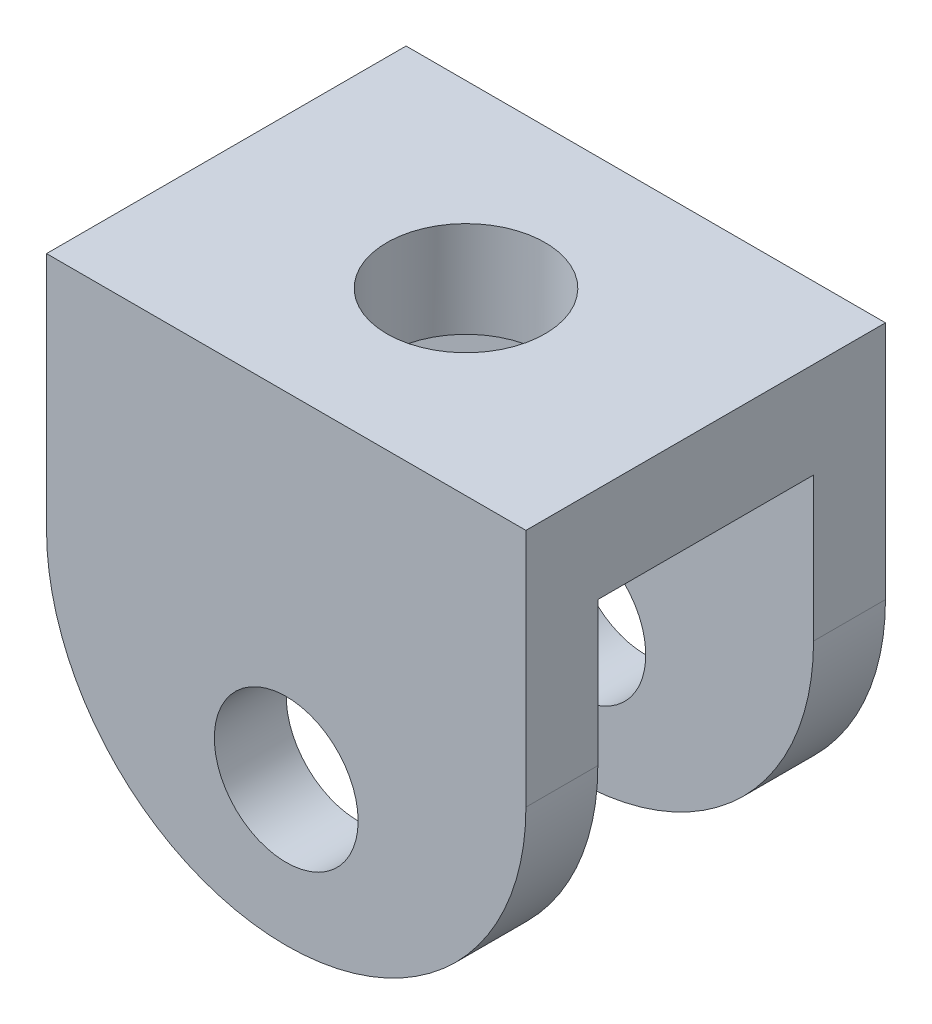
SolidWorks part; units mm, degrees
ref_plane "Front Plane" through (0, 0, 0) normal (0, 0, 1) x (1, 0, 0)
ref_plane "Top Plane" through (0, 0, 0) normal (0, 1, 0) x (1, 0, 0)
ref_plane "Right Plane" through (0, 0, 0) normal (1, 0, 0) x (0, 0, -1)
ref_axis "X-Axis" through (88.99, 0, 0) along (-1, 0, 0)
ref_axis "Y-Axis" through (0, 0, -88.99) along (0, 0, 1)
ref_axis "Z-Axis" through (0, -55, 0) along (0, 1, 0)
sketch "Sketch1" plane through (0, 0, 0) normal (0, 1, 0) x (1, 0, 0)
  line L1 (-10, -7.5) -> (10, -7.5)
  line L2 (-10, -7.5) -> (-10, 7.5)
  line L3 (-10, 7.5) -> (10, 7.5)
  line L4 (10, -7.5) -> (10, 7.5)
  line L5 (-10, -7.5) -> (10, 7.5) construction
  line L6 (-10, 7.5) -> (10, -7.5) construction
  point P0 (0, 0)
  dimension "D2" = 15
  dimension "D3" = 20
extrude "Boss-Extrude1" add sketch "Sketch1" along normal blind 4
sketch "Sketch3" plane through (0, 0, 0) normal (0, -1, 0) x (1, 0, 0)
  line L0 (10, 7.5) -> (10, -7.5) construction
  line L5 (-10, -7.5) -> (10, -7.5)
  line L6 (-10, -7.5) -> (-10, -4.5)
  line L7 (-10, -4.5) -> (10, -4.5)
  line L8 (10, -7.5) -> (10, -4.5)
  line L9 (-10, -7.5) -> (-10, 7.5) construction
  line L10 (10, 7.5) -> (-10, 7.5)
  line L11 (10, 7.5) -> (10, 4.5)
  line L12 (10, 4.5) -> (-10, 4.5)
  line L13 (-10, 7.5) -> (-10, 4.5)
  dimension "D1" = 3
  dimension "D2" = 3
extrude "Boss-Extrude2" add sketch "Sketch3" along normal blind 16
sketch "Sketch4" plane through (0, 4, 0) normal (0, 1, 0) x (1, 0, 0)
  point P0 (0, 0)
hole_wizard "M6 Clearance Hole1" positions "3DSketch1" profile "Sketch5" hole size "M6" standard "ANSI Metric"
sketch3d "3DSketch1"
  point P0 (0, 4, 0)
sketch "Sketch5" plane through (0, 4, 0) normal (1, 0, 0) x (0, 0, 1)
  line L0 (0, 0) -> (0, 9.9828)
  line L1 (0, 9.9828) -> (3.3, 8)
  line L2 (3.3, 8) -> (3.3, 0)
  line L5 (3.3, 0) -> (0, 0)
  line L10 (0, 9.9828) -> (-3.3, 8) construction
  line L11 (0, -6.35) -> (0, 107.95) construction
  dimension "Hole Dia." = 6.6
  dimension "Hole Depth" = 8
  dimension "Drill Angle" = 118
sketch "Sketch6" plane through (0, 0, -7.5) normal (0, 0, 1) x (1, 0, 0)
  line L1 (0, -55) -> (0, 55) construction
  line L2 (-10, -16) -> (10, -16) construction
  circle A0 centre (0, -10) radius 3
  point P2 (0, 0)
  dimension "D1" = 6
  dimension "D2" = 6
extrude "Cut-Extrude1" cut sketch "Sketch6" along normal blind 15
fillet "Fillet1" radius 10 4 edges at (10, -16, -6) (10, -16, 6) (-10, -16, 6) (-10, -16, -6)
